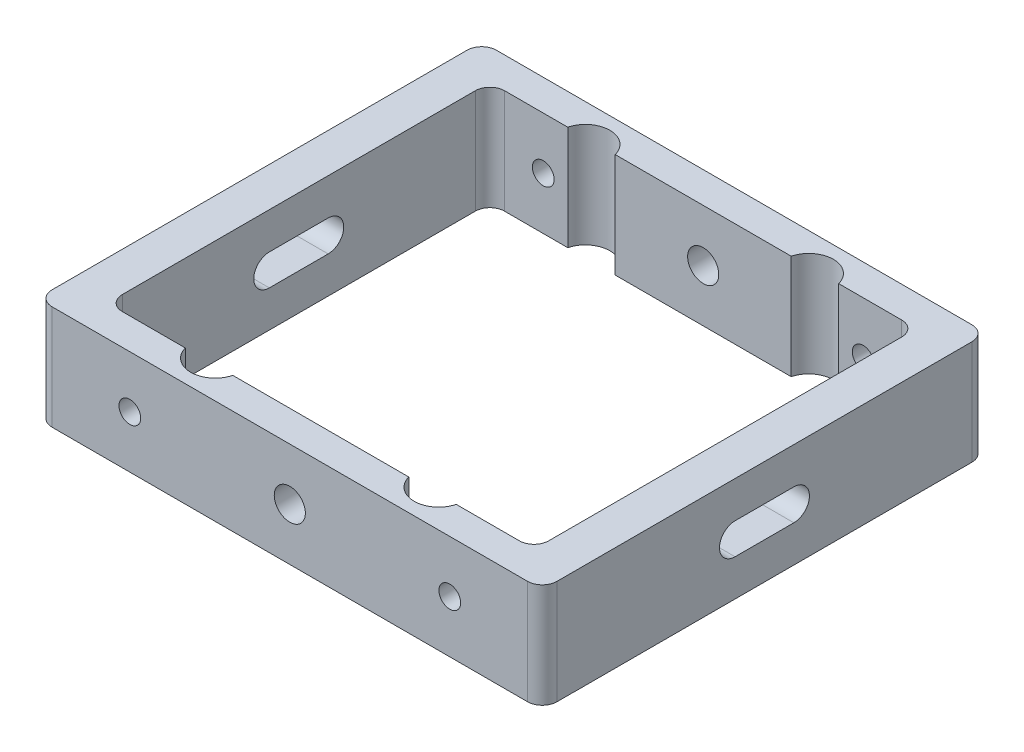
SolidWorks part; units mm, degrees
ref_plane "Front Plane" through (0, 0, 0) normal (0, 0, 1) x (1, 0, 0)
ref_plane "Top Plane" through (0, 0, 0) normal (0, 1, 0) x (1, 0, 0)
ref_plane "Right Plane" through (0, 0, 0) normal (1, 0, 0) x (0, 0, -1)
sketch "Sketch1" plane through (0, 0, 0) normal (0, 1, 0) x (1, 0, 0)
  line L1 (0, 0) -> (60, 0)
  line L2 (0, 0) -> (0, -6.32)
  line L3 (0, -6.32) -> (60, -6.32)
  line L4 (60, 0) -> (60, -6.32)
  dimension "D1" = 60
  dimension "D2" = 6.32
extrude "Boss-Extrude1" add sketch "Sketch1" along normal mid plane 21.28
sketch "Sketch2" plane through (0, 10.64, 0) normal (0, 1, 0) x (1, 0, 0)
  line L0 (0, 0) -> (0, -6.32) construction
  line L1 (0, -6.32) -> (60, -6.32) construction
  line L2 (60, -6.32) -> (60, 0) construction
  circle A0 centre (7.21, 1.25) radius 5
  circle A1 centre (52.79, 1.25) radius 5
  dimension "D1" = 7.21
  dimension "D3" = 7.21
  dimension "D2" = 7.57
  dimension "D4" = 7.57
extrude "Cut-Extrude1" cut sketch "Sketch2" against normal through all
sketch "Sketch3" plane through (60, 0, 0) normal (1, 0, 0) x (0, 0, -1)
  line L1 (-6.32, 10.64) -> (0, 10.64)
  line L2 (-6.32, 10.64) -> (-6.32, -10.64)
  line L3 (-6.32, -10.64) -> (0, -10.64)
  line L4 (0, 10.64) -> (0, -10.64)
extrude "Boss-Extrude2" add sketch "Sketch3" along normal blind 21.5
sketch "Sketch4" plane through (0, 0, 0) normal (-1, 0, 0) x (0, 0, 1)
  line L1 (0, 10.64) -> (6.32, 10.64)
  line L2 (0, 10.64) -> (0, -10.64)
  line L3 (0, -10.64) -> (6.32, -10.64)
  line L4 (6.32, 10.64) -> (6.32, -10.64)
extrude "Boss-Extrude3" add sketch "Sketch4" along normal blind 21.5
sketch "Sketch5" plane through (0, 0, 0) normal (0, 0, -1) x (-1, 0, 0)
  line L5 (-2.3688, -10.64) -> (21.5, -10.64) construction
  line L6 (21.5, 10.64) -> (13.5, 10.64)
  line L7 (21.5, 10.64) -> (21.5, -10.64)
  line L8 (21.5, -10.64) -> (13.5, -10.64)
  line L9 (13.5, 10.64) -> (13.5, -10.64)
  dimension "D1" = 8
extrude "Boss-Extrude6" add sketch "Sketch5" along normal blind 84.33
sketch "Sketch6" plane through (0, 0, 0) normal (0, 0, -1) x (-1, 0, 0)
  line L1 (-81.5, 10.64) -> (-73.5, 10.64)
  line L2 (-81.5, 10.64) -> (-81.5, -10.652)
  line L3 (-81.5, -10.652) -> (-73.5, -10.652)
  line L4 (-73.5, 10.64) -> (-73.5, -10.652)
  dimension "D1" = 8
extrude "Boss-Extrude7" add sketch "Sketch6" along normal blind 84.33
sketch "Sketch7" plane through (73.5, 0, 0) normal (-1, 0, 0) x (0, 0, 1)
  line L0 (-84.33, -10.652) -> (0, -10.652) construction
  line L1 (-84.33, 10.64) -> (-78.01, 10.64)
  line L2 (-84.33, 10.64) -> (-84.33, -10.652)
  line L3 (-84.33, -10.652) -> (-78.01, -10.652)
  line L4 (-78.01, 10.64) -> (-78.01, -10.652)
  dimension "D1" = 6.32
extrude "Boss-Extrude8" add sketch "Sketch7" along normal through all
sketch "Sketch9" plane through (0, 10.64, 0) normal (0, 1, 0) x (1, 0, 0)
  line L0 (-21.5, 84.33) -> (81.5, 84.33) construction
  circle A0 centre (7.21, 76.76) radius 5
  circle A1 centre (52.79, 76.76) radius 5
  dimension "D1" = 7.57
  dimension "D2" = 7.57
  dimension "D3" = 10
extrude "Cut-Extrude2" cut sketch "Sketch9" against normal through all
sketch "Sketch10" plane through (0, 0, -84.33) normal (0, 0, -1) x (-1, 0, 0)
  line L1 (-81.5, -10.64) -> (21.5, -10.64) construction
  line L2 (-30, -10.64) -> (-30, 10.64) construction
  line L3 (21.5, 10.64) -> (-81.5, 10.64) construction
  circle A0 centre (-62.6312, 0.005) radius 2.22
  circle A1 centre (2.6312, 0.005) radius 2.22
  dimension "D1" = 5
  dimension "D2" = 10.645
extrude "Cut-Extrude3" cut sketch "Sketch10" against normal through all
fillet "Fillet1" radius 3 8 edges at (-21.5, 0, 6.32) (81.5, 0, 6.32) (81.5, -0.006, -84.33) (-21.5, -0.006, -84.33) (-13.5, 0, -78.01) (-13.5, 0, 0) (73.5, -0.006, -78.01) (73.5, 0, 0)
sketch "Sketch13" plane through (0, 0, -84.33) normal (0, 0, -1) x (-1, 0, 0)
  line L1 (-78.5, 10.64) -> (-78.5, -10.652) construction
  line L2 (-78.5, -10.64) -> (18.5, -10.64) construction
  circle A0 centre (-30, 0.005) radius 3.175
  dimension "D1" = 48.5
  dimension "D3" = 6.35
  dimension "D2" = 10.645
extrude "Cut-Extrude4" cut sketch "Sketch13" against normal through all
sketch "Sketch16" plane through (0, -10.652, 0) normal (0, -1, 0) x (1, 0, 0)
  line L6 (78.5, -84.33) -> (-18.5, -84.33) construction
  line L7 (25.5729, -84.33) -> (12.6189, -84.33)
  line L8 (25.5729, -84.33) -> (25.5729, -78.01)
  line L9 (25.5729, -78.01) -> (12.6189, -78.01)
  line L10 (12.6189, -84.33) -> (12.6189, -78.01)
  line L11 (12.0512, -78.01) -> (47.9488, -78.01) construction
  dimension "D1" = 12.954
extrude "Cut-Extrude6" [suppressed] cut sketch "Sketch16" against normal mid plane 25.4
sketch "Sketch18" plane through (-21.5, 0, 0) normal (-1, 0, 0) x (0, 0, 1)
  line L0 (-81.33, 10.64) -> (-81.33, -10.652) construction
  line L1 (-75.01, -10.652) -> (0, -10.652) construction
  line L2 (-45.005, 3.168) -> (-33.005, 3.168)
  line L4 (-33.005, -3.182) -> (-45.005, -3.182)
  arc A0 (-45.005, 3.168) -> (-45.005, -3.182) centre (-45.005, -0.007) ccw
  arc A1 (-33.005, -3.182) -> (-33.005, 3.168) centre (-33.005, -0.007) ccw
  dimension "D1" = 36.325
  dimension "D3" = 12
  dimension "D2" = 10.645
extrude "Cut-Extrude7" cut sketch "Sketch18" against normal through all
